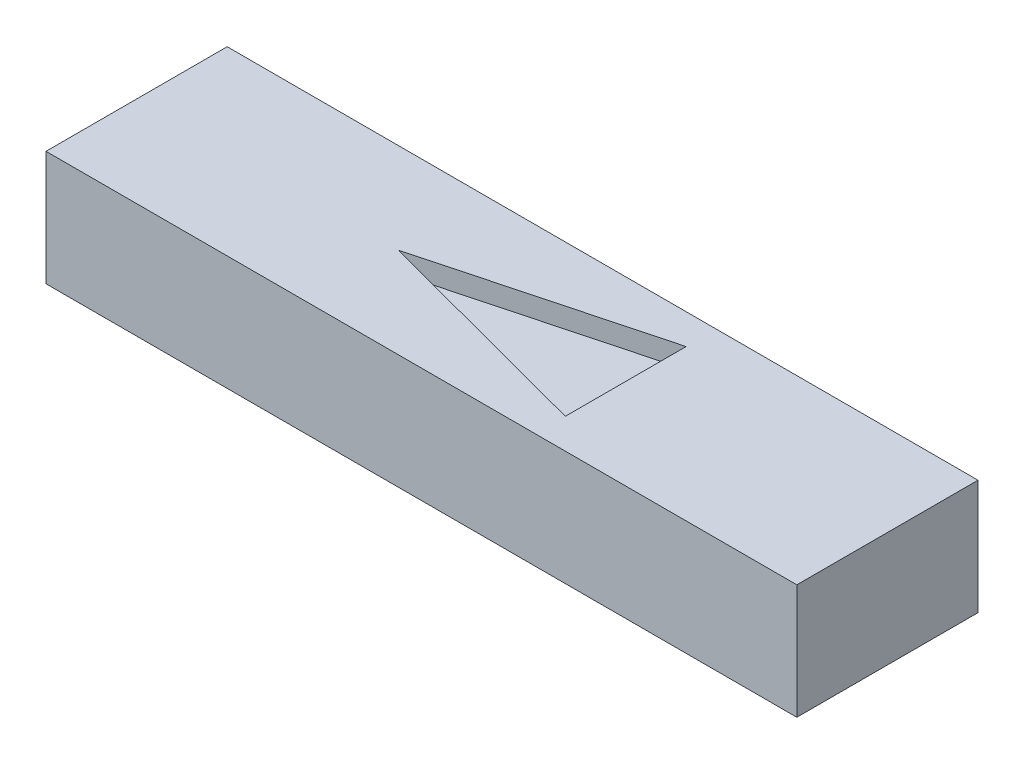
SolidWorks part; units mm, degrees
ref_plane "Front Plane" through (0, 0, 0) normal (0, 0, 1) x (1, 0, 0)
ref_plane "Top Plane" through (0, 0, 0) normal (0, 1, 0) x (1, 0, 0)
ref_plane "Right Plane" through (0, 0, 0) normal (1, 0, 0) x (0, 0, -1)
sketch "Sketch2" plane through (0, 0, 0) normal (0, 1, 0) x (1, 0, 0)
  line L1 (0, 0) -> (37.3, 0)
  line L2 (0, 0) -> (0, 9)
  line L3 (0, 9) -> (37.3, 9)
  line L4 (37.3, 0) -> (37.3, 9)
  dimension "D1" = 37.3
  dimension "D2" = 9
extrude "Boss-Extrude1" add sketch "Sketch2" along normal blind 5.7
sketch "Sketch3" plane through (0, 5.7, 0) normal (0, 1, 0) x (1, 0, 0)
  line L0 (0, 0) -> (37.3, 0) construction
  line L1 (24.3, 1.5) -> (13, 1.5)
  line L2 (24.3, 1.5) -> (24.3, 7.5)
  line L3 (24.3, 7.5) -> (13, 7.5)
  line L4 (13, 1.5) -> (13, 7.5)
  line L5 (37.3, 9) -> (0, 9) construction
  line L6 (0, 9) -> (0, 0) construction
  line L7 (37.3, 0) -> (37.3, 9) construction
  line L8 (24.3, 7.5) -> (13, 4.5)
  line L9 (13, 4.5) -> (24.3, 1.5)
  dimension "D1" = 1.5
  dimension "D3" = 1.5
  dimension "D4" = 13
  dimension "D5" = 13
extrude "Cut-Extrude1" cut sketch "Sketch3" against normal blind 1 contours L8 L9 L2 region at (20.5333, 5.7, -4.5)
